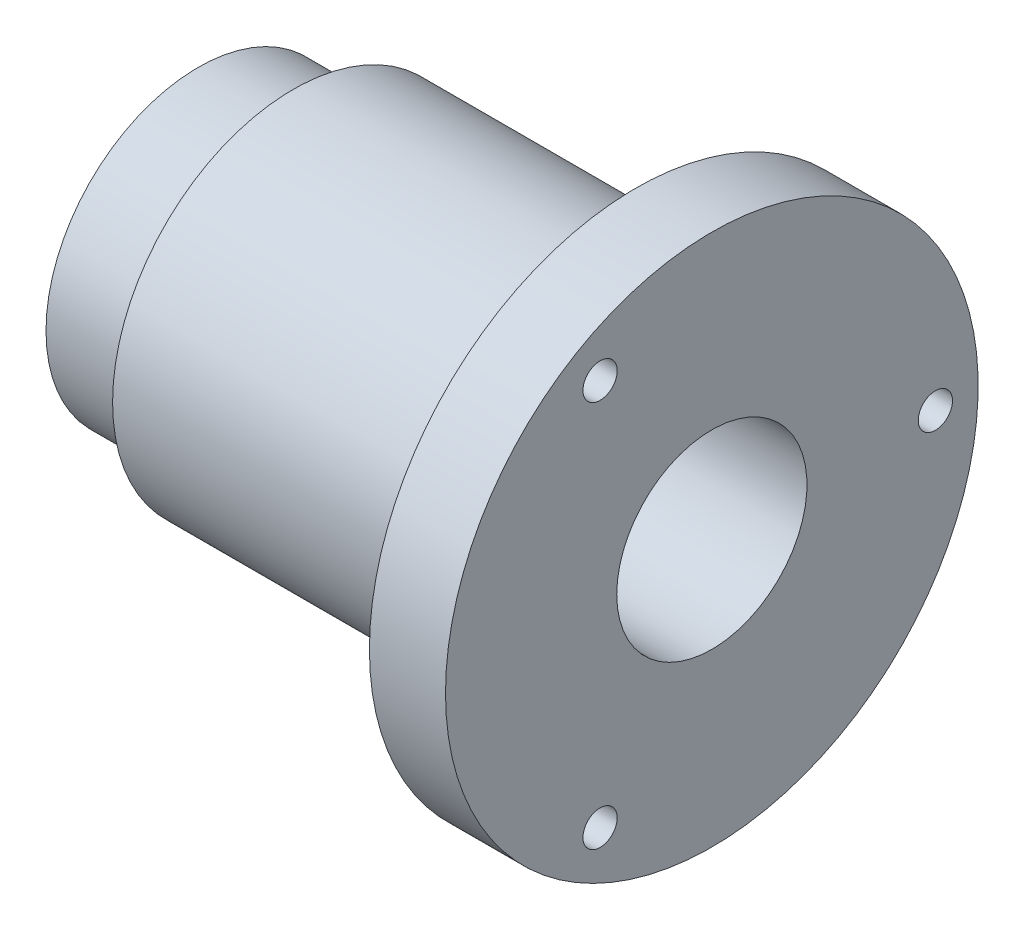
SolidWorks part; units mm, degrees
ref_plane "Front Plane" through (0, 0, 0) normal (0, 0, 1) x (1, 0, 0)
ref_plane "Top Plane" through (0, 0, 0) normal (0, 1, 0) x (1, 0, 0)
ref_plane "Right Plane" through (0, 0, 0) normal (1, 0, 0) x (0, 0, -1)
sketch "Sketch1" plane through (0, 0, 0) normal (0, 1, 0) x (1, 0, 0)
  line L0 (0, 0) -> (23.1328, 0) construction
  line L1 (0, 5) -> (27, 5)
  line L2 (0, 5) -> (0, 8)
  line L3 (0, 8) -> (5, 8)
  line L4 (5, 8) -> (5, 9.5)
  line L5 (5, 9.5) -> (23, 9.5)
  line L6 (23, 9.5) -> (23, 14)
  line L7 (23, 14) -> (27, 14)
  line L8 (27, 14) -> (27, 5)
  dimension "D1" = 10
  dimension "D2" = 19
  dimension "D3" = 3
  dimension "D4" = 5
  dimension "D5" = 18
  dimension "D6" = 28
  dimension "D7" = 4
revolve "Revolve1" add sketch "Sketch1" angle 360 about L0
sketch "Sketch2" plane through (23, 0, 0) normal (-1, 0, 0) x (0, 0, 1)
  line L1 (-9.5, 0) -> (-14, 0) construction
  circle A0 centre (0, 0) radius 9.5 construction
  circle A1 centre (0, 0) radius 14 construction
  circle A2 centre (-11.75, 0) radius 0.9
  dimension "D1" = 1.8
extrude "Cut-Extrude1" cut sketch "Sketch2" against normal through all
pattern_circular "CirPattern1" count 3 over 360 about axis through (0, 0, 0) along (-1, 0, 0) of "Cut-Extrude1"
